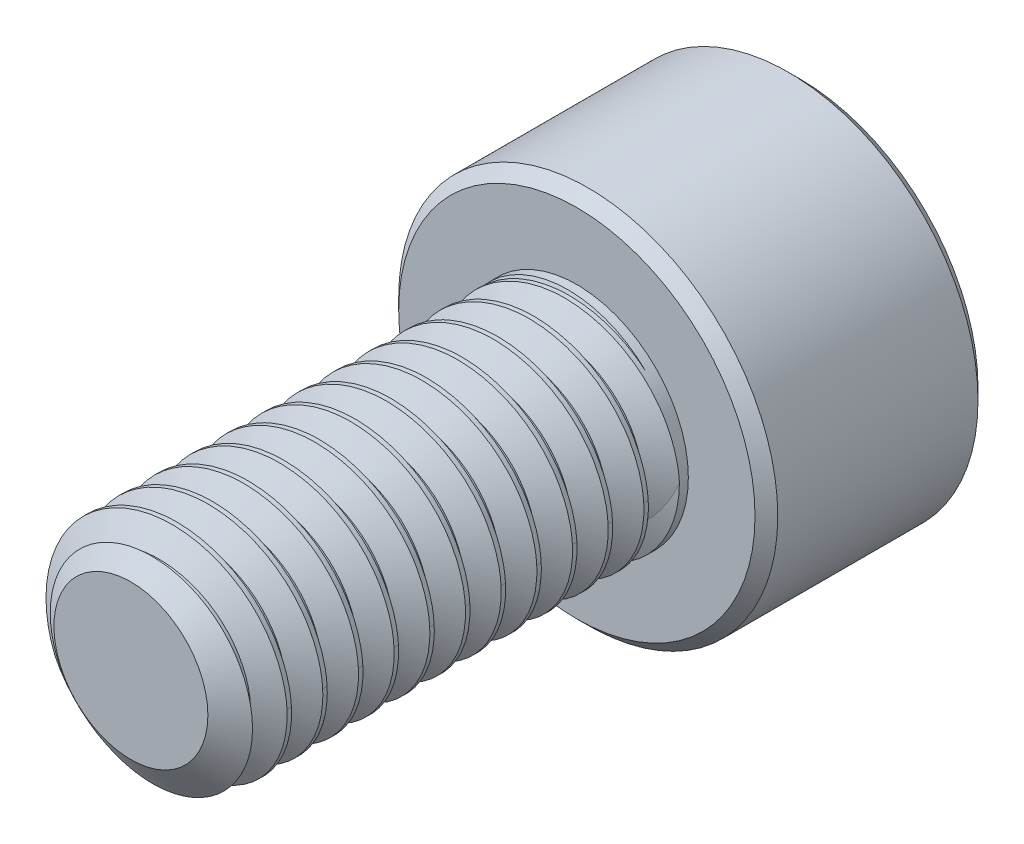
SolidWorks part; units mm, degrees
ref_plane "Front Plane" through (0, 0, 0) normal (0, 0, 1) x (1, 0, 0)
ref_plane "Top Plane" through (0, 0, 0) normal (0, 1, 0) x (1, 0, 0)
ref_plane "Right Plane" through (0, 0, 0) normal (1, 0, 0) x (0, 0, -1)
sketch "Sketch1" plane through (0, 0, 0) normal (0, 0, 1) x (1, 0, 0)
  circle A0 centre (0, 0) radius 2.5
  dimension "OD" = 5
extrude "Extrude1" add sketch "Sketch1" against normal blind 10
sketch "Sketch2" plane through (0, 0, 0) normal (0, 0, 1) x (1, 0, 0)
  circle A0 centre (0, 0) radius 2.5 construction
  circle A1 centre (0, 0) radius 2.5
curve "Helix/Spiral1" pitch 0.8 height 10.8 turns 13.5 parameters "pitch"=0.8
sketch "Sketch3" plane through (0, 0, 0) normal (1, 0, 0) x (0, 0, -1)
  line L0 (-0.7, 2.5) -> (-0.4, 1.9804)
  line L1 (-0.4, 1.9804) -> (-0.3, 1.9804)
  line L2 (-0.3, 1.9804) -> (0, 2.5)
  line L3 (-0.7, 2.5) -> (0, 2.5)
  line L4 (-0.35, 2.5) -> (-0.35, 1.9804) construction
  line L5 (-0.55, 2.2402) -> (-0.15, 2.2402) construction
  line L6 (0, 2.5) -> (0, -2.5) construction
  line L7 (0, -2.5) -> (10, -2.5) construction
  point P11 (3.6, -2.5)
  dimension "D1" = 0.1
  dimension "D2" = 0.4
  dimension "D3" = 60
  dimension "D4" = 3.6
sweep "Cut-Sweep1" cut profiles "Sketch3" path "Helix/Spiral1"
sketch "Sketch4" plane through (0, 0, 0) normal (1, 0, 0) x (0, 0, -1)
  line L0 (0.5417, 2.5) -> (0, 1.7264)
  line L1 (0, 1.7264) -> (0, 2.5)
  line L2 (0.5417, 2.5) -> (0, 2.5)
  line L3 (-0.7, 2.5) -> (0, 2.5) construction
  line L4 (0, 0) -> (7.0209, 0) construction
  dimension "D1" = 55
  dimension "D2" = 0.254
revolve "Cut-Revolve1" cut sketch "Sketch4" angle 360 about L4
sketch "Sketch5" plane through (0, 0, 0) normal (1, 0, 0) x (0, 0, -1)
  line L0 (10, -1.7838) -> (10, 1.991) construction
  line L1 (10, 2.5) -> (0.1203, 2.5)
  line L2 (10, 2.5) -> (10, 0)
  line L3 (10, 0) -> (0.0001, 0)
  line L4 (0.0001, 2.1698) -> (0.0001, 0)
  line L5 (0.1203, 2.5) -> (0.0001, 2.1698)
  line L6 (0, 0) -> (9.9695, 0) construction
  point P3 (0.0001, 2.5)
  point P10 (0.0001, 2.5)
  dimension "D1" = 0.3302
  dimension "Thread min" = 0.0001
  dimension "D3" = 20
revolve "partially thread" [suppressed] add sketch "Sketch5" angle 360 about L6
sketch "Sketch6" plane through (0, 0, -10) normal (0, 0, -1) x (-1, 0, 0)
  circle A0 centre (0, 0) radius 4.25
  dimension "head dia" = 8.5
extrude "Extrude2" add sketch "Sketch6" along normal blind 5
sketch "Sketch7" plane through (0, 0, -15) normal (0, 0, -1) x (-1, 0, 0)
  line L1 (0, 2.3094) -> (-2, 1.1547)
  line L2 (-2, 1.1547) -> (-2, -1.1547)
  line L3 (-2, -1.1547) -> (0, -2.3094)
  line L4 (0, -2.3094) -> (2, -1.1547)
  line L5 (2, -1.1547) -> (2, 1.1547)
  line L6 (2, 1.1547) -> (0, 2.3094)
  circle A0 centre (0, 0) radius 2 construction
  dimension "hex dia" = 4
extrude "Cut-Extrude1" cut sketch "Sketch7" against normal blind 3
sketch "Sketch8" plane through (0, 0, -15) normal (0, 0, -1) x (-1, 0, 0)
  circle A0 centre (0, 0) radius 2.3094
extrude "Cut-Extrude2" cut sketch "Sketch8" against normal through all draft 45
chamfer "Chamfer1" distance 0.255 angle 45 2 edges at (-4.25, 0, -15) (-4.25, 0, -10)
sketch "Sketch9" plane through (0, 0, 0) normal (1, 0, 0) x (0, 0, -1)
  line L0 (0, 2.5) -> (0, -2.5) construction
  line L1 (4.4, 2.5) -> (4.4, -2.5) construction
  dimension "D1" = 4.4
sketch "Sketch10" plane through (0, 0, 0) normal (1, 0, 0) x (0, 0, -1)
  line L0 (10, 2.5) -> (10, 0)
  line L1 (10, 2.5) -> (9.8, 2.5)
  line L2 (9.8, 2.5) -> (8.7645, 0)
  line L3 (10, 0) -> (8.7645, 0)
  line L4 (10, 3.995) -> (10, -3.995) construction
  dimension "D1" = 22.5
  dimension "D2" = 0.2
revolve "Revolve1" add sketch "Sketch10" angle 360 about L3
equation "\"D3@Helix/Spiral1\" = \"screw length@Extrude1\"+\"pitch@Helix/Spiral1\""
equation "\"D1@Sketch3\" = \"pitch@Helix/Spiral1\"*.125"
equation "\"D2@Sketch3\" = \"pitch@Helix/Spiral1\"*.5"
equation "\"D1@Cut-Extrude1\" = \"hex dia@Sketch7\"*.75"
equation "\"D1@Chamfer1\" = \"head dia@Sketch6\"*.03"
equation "\"D1@Sketch9\" = \"pitch@Helix/Spiral1\"*5.5"
equation "\"D2@Sketch10\" = \"pitch@Helix/Spiral1\"*.25"
equation "\"D4@Sketch3\" = \"pitch@Helix/Spiral1\"*4.50"
